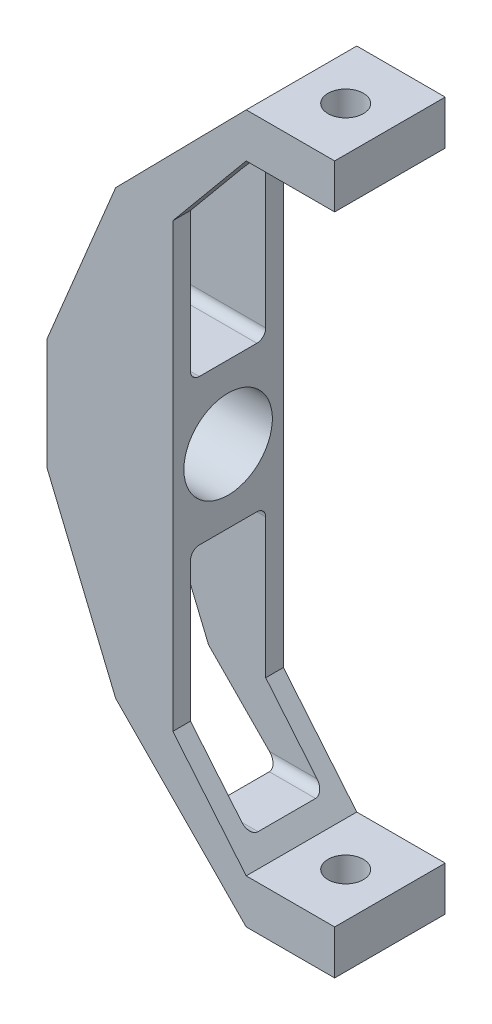
SolidWorks part; units mm, degrees
ref_plane "Front Plane" through (0, 0, 0) normal (0, 0, 1) x (1, 0, 0)
ref_plane "Top Plane" through (0, 0, 0) normal (0, 1, 0) x (1, 0, 0)
ref_plane "Right Plane" through (0, 0, 0) normal (1, 0, 0) x (0, 0, -1)
sketch "Sketch1" plane through (0, 0, 0) normal (0, 0, 1) x (1, 0, 0)
  line L0 (0, 0) -> (-20, 0)
  line L2 (-20, -160) -> (0, -160)
  line L3 (0, -160) -> (0, -150)
  line L4 (0, -150) -> (-20, -150)
  line L5 (-36.59, -130) -> (-36.59, -30)
  line L6 (-20, -10) -> (0, -10)
  line L7 (0, -10) -> (0, 0)
  line L13 (-10, 0) -> (-10, -160) construction
  line L14 (-49.5183, -30) -> (-65.09, -67.5)
  line L15 (-65.09, -67.5) -> (-65.09, -92.5)
  line L16 (-65.09, -92.5) -> (-49.5183, -130)
  line L17 (-36.59, -30) -> (-20, -10)
  line L18 (-36.59, -130) -> (-20, -150)
  line L19 (-36.59, -30) -> (-49.5183, -30) construction
  line L20 (-49.5183, -30) -> (-20, 0)
  line L21 (-36.59, -130) -> (-49.5183, -130) construction
  line L22 (-49.5183, -130) -> (-20, -160)
  point P4 (-36.59, -80)
  point P8 (-65.09, -80)
  point P14 (-10, -80)
  dimension "D8" = 100
  dimension "D1" = 26.59
  dimension "D2" = 140
  dimension "D3" = 10
  dimension "D5" = 10
  dimension "D6" = 10
  dimension "D7" = 10
  dimension "D9" = 28.5
  dimension "D10" = 25
  dimension "D11" = 10
  dimension "D12" = 10
extrude "Boss-Extrude1" add sketch "Sketch1" along normal blind 25
sketch "Sketch3" plane through (-65.09, 0, 0) normal (-1, 0, 0) x (0, 0, 1)
  line L1 (6, -63.5) -> (19, -63.5)
  line L2 (4, -61.5) -> (4, -15.9991)
  line L3 (6, -13.9991) -> (19, -13.9991)
  line L4 (21, -61.5) -> (21, -15.9991)
  line L5 (25, -5.5591) -> (0, -5.5591) construction
  line L6 (25, -30) -> (25, -67.5) construction
  line L7 (0, -30) -> (0, -67.5) construction
  line L8 (25, -67.5) -> (0, -67.5) construction
  line L9 (0, -80) -> (25, -80) construction
  line L10 (0, -67.5) -> (0, -92.5) construction
  line L11 (25, -67.5) -> (25, -92.5) construction
  line L12 (6, -146.0009) -> (19, -146.0009)
  line L13 (21, -98.5) -> (21, -144.0009)
  line L14 (6, -96.5) -> (19, -96.5)
  line L15 (4, -98.5) -> (4, -144.0009)
  arc A0 (6, -63.5) -> (4, -61.5) centre (6, -61.5) cw
  arc A1 (19, -63.5) -> (21, -61.5) centre (19, -61.5) ccw
  arc A2 (19, -13.9991) -> (21, -15.9991) centre (19, -15.9991) cw
  arc A3 (4, -15.9991) -> (6, -13.9991) centre (6, -15.9991) cw
  arc A4 (19, -146.0009) -> (21, -144.0009) centre (19, -144.0009) ccw
  arc A5 (19, -96.5) -> (21, -98.5) centre (19, -98.5) cw
  arc A6 (6, -96.5) -> (4, -98.5) centre (6, -98.5) ccw
  arc A7 (4, -144.0009) -> (6, -146.0009) centre (6, -144.0009) ccw
  circle A8 centre (12.5, -80) radius 10
  dimension "D5" = 2
  dimension "D6" = 20
  dimension "D1" = 8.44
  dimension "D2" = 4
  dimension "D3" = 4
  dimension "D4" = 4
extrude "Cut-Extrude2" cut sketch "Sketch3" against normal through all
sketch "Sketch4" plane through (0, 0, 0) normal (0, 1, 0) x (1, 0, 0)
  line L0 (-10, 0) -> (-10, -25) construction
  line L1 (0, 0) -> (-20, 0) construction
  line L2 (0, -25) -> (-20, -25) construction
  line L3 (-36.59, -25) -> (-36.59, -21) construction
  circle A0 centre (-10, -12.5) radius 4
  dimension "D2" = 8
  dimension "D1" = 26.59
extrude "Cut-Extrude3" cut sketch "Sketch4" against normal through all
